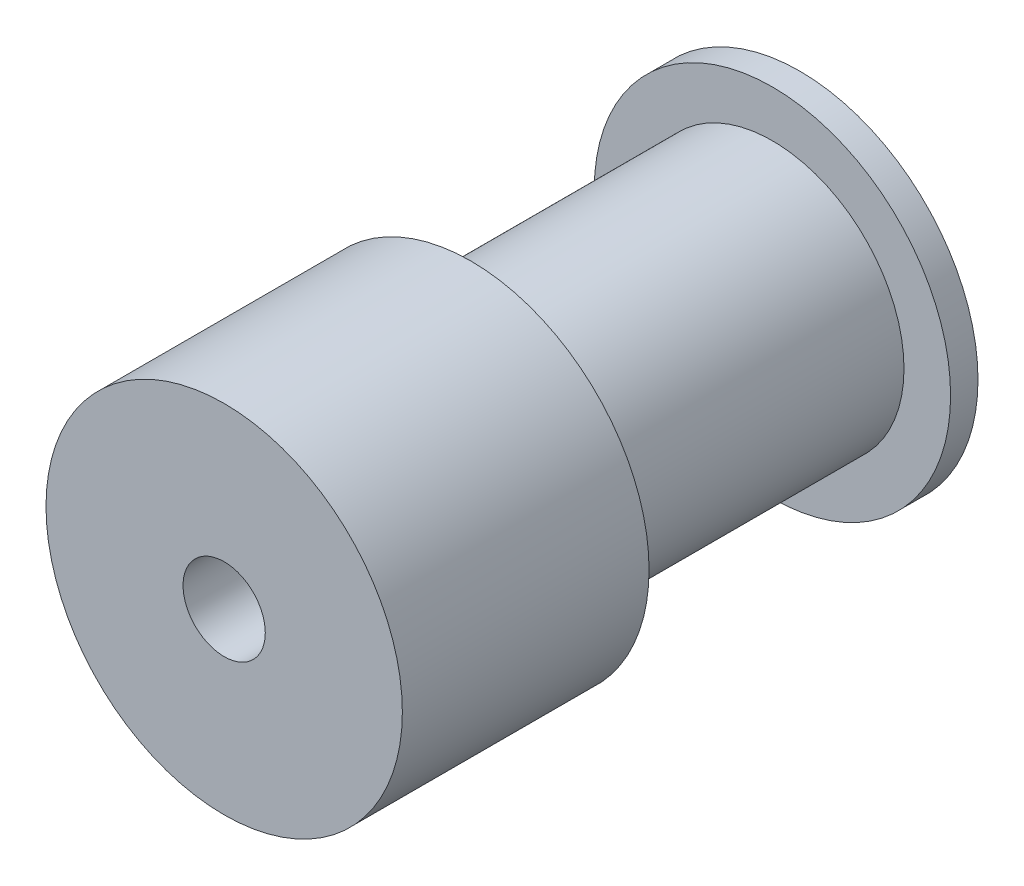
SolidWorks part; units mm, degrees
ref_plane "Front Plane" through (0, 0, 0) normal (0, 0, 1) x (1, 0, 0)
ref_plane "Top Plane" through (0, 0, 0) normal (0, 1, 0) x (1, 0, 0)
ref_plane "Right Plane" through (0, 0, 0) normal (1, 0, 0) x (0, 0, -1)
sketch "Sketch1" plane through (0, 0, 0) normal (0, 0, 1) x (1, 0, 0)
  circle A0 centre (0, 0) radius 6.5
  circle A1 centre (0, 0) radius 1.5
  dimension "D1" = 13
  dimension "D2" = 3
extrude "Boss-Extrude1" add sketch "Sketch1" along normal blind 1
sketch "Sketch2" plane through (0, 0, 1) normal (0, 0, 1) x (1, 0, 0)
  circle A0 centre (0, 0) radius 1.5
  circle A1 centre (0, 0) radius 4.8
  dimension "D1" = 3
  dimension "D2" = 9.6
extrude "Boss-Extrude2" add sketch "Sketch2" along normal blind 7
sketch "Sketch3" plane through (0, 0, 8) normal (0, 0, 1) x (1, 0, 0)
  circle A0 centre (0, 0) radius 1.5
  circle A1 centre (0, 0) radius 6.5
  dimension "D1" = 13
  dimension "D2" = 3
extrude "Boss-Extrude3" add sketch "Sketch3" along normal blind 1
sketch "Croquis2" plane through (0, 0, 9) normal (0, 0, 1) x (1, 0, 0)
  circle A0 centre (0, 0) radius 6.5
  circle A1 centre (0, 0) radius 1.5
  dimension "D1" = 13
  dimension "D2" = 3
extrude "Saliente-Extruir1" add sketch "Croquis2" along normal blind 12
sketch "Croquis3" plane through (0, 0, 8) normal (0, 0, -1) x (-1, 0, 0)
  circle A0 centre (0, 0) radius 4.8
  circle A1 centre (0, 0) radius 6.5
  dimension "D1" = 9.6
  dimension "D2" = 13
extrude "Cortar-Extruir2" cut sketch "Croquis3" against normal blind 4
